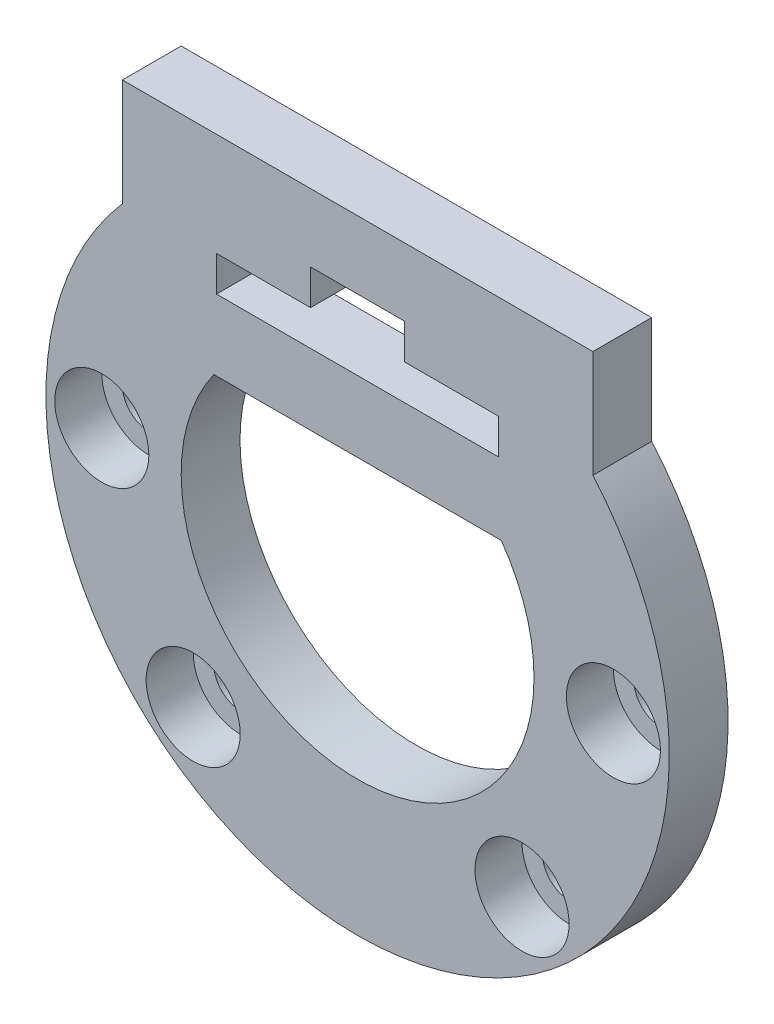
SolidWorks part; units mm, degrees
ref_plane "前视基准面" through (0, 0, 0) normal (0, 0, 1) x (1, 0, 0)
ref_plane "上视基准面" through (0, 0, 0) normal (0, 1, 0) x (1, 0, 0)
ref_plane "右视基准面" through (0, 0, 0) normal (1, 0, 0) x (0, 0, -1)
sketch "草图1" plane through (0, 0, 0) normal (0, 0, 1) x (1, 0, 0)
  line L1 (0, 26.5) -> (20, 26.5)
  line L2 (0, 26.5) -> (-20, 26.5)
  line L3 (-20, 26.5) -> (-20, 17.3853)
  line L4 (20, 26.5) -> (20, 17.3853)
  arc A1 (-20, 17.3853) -> (20, 17.3853) centre (0, 0) ccw
extrude "凸台-拉伸1" add sketch "草图1" along normal blind 5
hole_wizard "M4 六角凹头盖的柱孔1" positions "3D草图2" profile "草图3" counterbore size "M4" standard "BSI" end condition through all
sketch3d "3D草图2"
  point P38 (-21.75, 0, 5)
  point P40 (-13.9806, -16.6615, 5)
  point P42 (13.9806, -16.6615, 5)
  point P44 (21.75, 0, 5)
  point P46 (0, 0, 0)
  point P47 (0, 0, 0)
  point P48 (0, 0, 0)
sketch "草图3" plane through (-21.75, 0, 5) normal (1, 0, 0) x (0, -1, 0)
  line L0 (0, 0) -> (0, 5)
  line L1 (0, 5) -> (2.25, 5)
  line L3 (2.25, 5) -> (2.25, 4)
  line L4 (2.25, 4) -> (4, 4)
  line L5 (4, 4) -> (4, 0)
  line L7 (4, 0) -> (0, 0)
  line L11 (0, -6.35) -> (0, 107.95) construction
  dimension "通孔孔直径" = 4.5
  dimension "通孔孔深度" = 5
  dimension "柱形沉头孔直径" = 8
  dimension "柱形沉头孔深度" = 4
ref_plane "基准面1" through (0, 0, 5) normal (0, 0, 1) x (1, 0, 0)
sketch "草图17" plane through (0, 0, 5) normal (0, 0, 1) x (1, 0, 0)
  line L18 (-4, 17.7317) -> (-4, 20.7317)
  line L26 (4, 20.7317) -> (-4, 20.7317)
  line L28 (-9, 14.7317) -> (9, 14.7317)
  line L33 (-4, 17.7317) -> (-12, 17.7317)
  line L34 (-12, 17.7317) -> (-12, 14.7317)
  line L35 (-12, 14.7317) -> (-9, 14.7317)
  line L37 (12, 14.7317) -> (9, 14.7317)
  line L38 (12, 17.7317) -> (12, 14.7317)
  line L39 (4, 17.7317) -> (12, 17.7317)
  line L40 (4, 17.7317) -> (4, 20.7317)
extrude "切除-拉伸5" cut sketch "草图17" against normal blind 10
sketch "草图18" plane through (0, 0, 5) normal (0, 0, 1) x (1, 0, 0)
  line L1 (-7.9819, 8.7) -> (-12.2192, 8.7)
  line L3 (-7.9819, 8.7) -> (12.2192, 8.7)
  arc A2 (12.2192, 8.7) -> (-12.2192, 8.7) centre (0, 0) cw
extrude "切除-拉伸6" cut sketch "草图18" against normal blind 10
